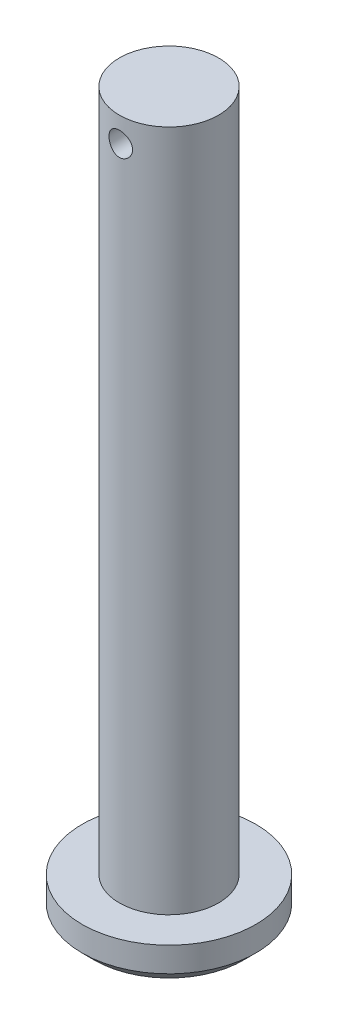
SolidWorks part; units mm, degrees
ref_plane "Front Plane" through (0, 0, 0) normal (0, 0, 1) x (1, 0, 0)
ref_plane "Top Plane" through (0, 0, 0) normal (0, 1, 0) x (1, 0, 0)
ref_plane "Right Plane" through (0, 0, 0) normal (1, 0, 0) x (0, 0, -1)
sketch "Sketch1" plane through (0, 0, 0) normal (0, 1, 0) x (1, 0, 0)
  circle A0 centre (0, 0) radius 7
  circle A1 centre (0, 0) radius 4
  dimension "D1" = 14
  dimension "D2" = 8
extrude "Boss-Extrude1" add sketch "Sketch1" against normal blind 3 contours A0
extrude "Boss-Extrude2" add sketch "Sketch1<3>" along normal blind 55 contours A1
sketch "Sketch1<3>" plane through (0, 0, 0) normal (0, 1, 0) x (1, 0, 0) same geometry as "Sketch1"
ref_plane "Plane1" through (0, 0, -4) normal (0, 0, -1) x (-1, 0, 0)
sketch "Sketch2" plane through (0, 0, -4) normal (0, 0, -1) x (-1, 0, 0)
  line L0 (4, 55) -> (-4, 55) construction
  circle A0 centre (0, 53) radius 0.95
  dimension "D2" = 1.9
  dimension "D1" = 2
extrude "Cut-Extrude1" cut sketch "Sketch2" against normal through all
chamfer "Chamfer1" distance 1 angle 45 1 edges at (0, -3, 7)
